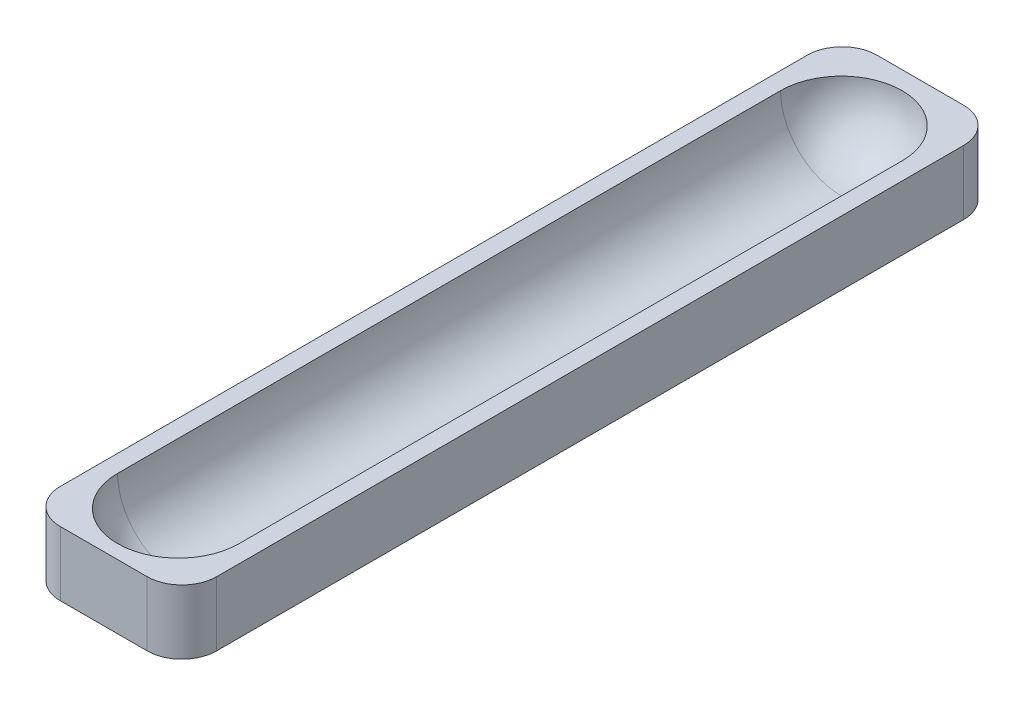
SolidWorks part; units mm, degrees
material "AISI 4340 Steel, normalized"
ref_plane "Front Plane" through (0, 0, 0) normal (0, 0, 1) x (1, 0, 0)
ref_plane "Top Plane" through (0, 0, 0) normal (0, 1, 0) x (1, 0, 0)
ref_plane "Right Plane" through (0, 0, 0) normal (1, 0, 0) x (0, 0, -1)
sketch "Sketch1" plane through (0, 0, 0) normal (0, 1, 0) x (1, 0, 0)
  line L0 (-57.15, 54.5595) -> (-57.15, 539.2088) construction
  line L1 (0, 0) -> (-114.3, 0)
  line L2 (0, 0) -> (0, 596.9)
  line L3 (0, 596.9) -> (-114.3, 596.9)
  line L4 (-114.3, 0) -> (-114.3, 596.9)
  line L5 (-101.6, 54.5595) -> (-101.6, 539.2088)
  line L6 (-12.7, 54.5595) -> (-12.7, 539.2088)
  arc A1 (-101.6, 54.5595) -> (-12.7, 54.5595) centre (-57.15, 54.5595) ccw
  arc A2 (-12.7, 539.2088) -> (-101.6, 539.2088) centre (-57.15, 539.2088) ccw
  point P7 (-101.6, 298.45)
  point P8 (-114.3, 298.45)
  point P10 (-57.15, 596.9)
  point P13 (-57.15, 342.9)
  point P15 (-57.15, 296.8841)
  dimension "D2" = 254
  dimension "D4" = 44.45
  dimension "D3" = 12.7
extrude "Boss-Extrude1" add sketch "Sketch1" along normal blind 46.99 contours L4 L1 L2 L3 | L6 A2 L5 A1 region at (-57.15, 0, -6.0775) region at (-57.15, 0, -296.8841)
sketch "Sketch2" plane through (0, 46.99, 0) normal (0, 1, 0) x (1, 0, 0)
  line L0 (-57.15, 596.9) -> (-57.15, 0) construction
  line L1 (0, 596.9) -> (-114.3, 596.9) construction
  line L2 (0, 0) -> (-114.3, 0) construction
  line L6 (-101.6, 539.2088) -> (-101.6, 54.5595)
  line L7 (-12.7, 54.5595) -> (-12.7, 539.2088)
  line L8 (-114.3, 0) -> (0, 0)
  line L9 (-114.3, 596.9) -> (-114.3, 0)
  line L10 (0, 596.9) -> (-114.3, 596.9)
  line L11 (0, 0) -> (0, 596.9)
  line L12 (-114.3, 0) -> (0, 0)
  line L13 (-114.3, 596.9) -> (-114.3, 0)
  line L14 (0, 596.9) -> (-114.3, 596.9)
  line L15 (0, 0) -> (0, 596.9)
  line L16 (-101.6, 539.2088) -> (-101.6, 54.5595)
  line L17 (-12.7, 54.5595) -> (-12.7, 539.2088)
  arc A3 (-12.7, 539.2088) -> (-101.6, 539.2088) centre (-57.15, 539.2088) ccw
  arc A4 (-101.6, 54.5595) -> (-12.7, 54.5595) centre (-57.15, 54.5595) ccw
  arc A5 (-12.7, 539.2088) -> (-101.6, 539.2088) centre (-57.15, 539.2088) ccw
  arc A6 (-101.6, 54.5595) -> (-12.7, 54.5595) centre (-57.15, 54.5595) ccw
  dimension "D2" = 0
  dimension "D3" = 0
revolve "Cut-Revolve1" cut sketch "Sketch2" angle 180 about L0 region at (-35.3481, 46.99, -296.8841) reverse direction yes
sketch "Sketch5" plane through (0, 0, 0) normal (0, -1, 0) x (1, 0, 0)
  line L0 (-57.15, 0) -> (-57.15, -596.9) construction
  line L1 (0, 0) -> (-114.3, 0) construction
  line L2 (0, -596.9) -> (-114.3, -596.9) construction
  line L3 (-57.15, -298.45) -> (0, -298.45) construction
  line L4 (0, 0) -> (0, -596.9) construction
  line L5 (-57.15, -298.45) -> (-114.3, -298.45) construction
  line L6 (-114.3, 0) -> (-114.3, -596.9) construction
  line L7 (-114.3, -44.45) -> (0, -44.45) construction
  line L8 (-114.3, -552.45) -> (0, -552.45) construction
  point P17 (-57.15, -44.45)
  point P18 (-57.15, -552.45)
  point P19 (-57.15, -298.45)
  dimension "D1" = 44.45
  dimension "D2" = 44.45
fillet "Fillet1" radius 25.4 4 edges at (0, 23.495, 0) (-114.3, 23.495, 0) (-114.3, 23.495, -596.9) (0, 23.495, -596.9)
sketch "Sketch3" [suppressed] plane through (0, 0, 0) normal (0, -1, 0) x (1, 0, 0)
  line L0 (-57.15, -114.3) -> (-57.15, 0) construction
  line L1 (-25.4, -114.3) -> (-88.9, -114.3) construction
  line L2 (-25.4, 0) -> (-88.9, 0) construction
  line L3 (0, -57.15) -> (-114.3, -57.15) construction
  line L4 (0, -25.4) -> (0, -88.9) construction
  line L5 (-114.3, -25.4) -> (-114.3, -88.9) construction
sketch "Sketch4" [suppressed] plane through (0, 0, 0) normal (0, -1, 0) x (1, 0, 0)
  line L0 (0, -57.15) -> (-114.3, -57.15) construction
  line L1 (0, -25.4) -> (0, -88.9) construction
  line L2 (-114.3, -25.4) -> (-114.3, -88.9) construction
  line L3 (-57.15, -114.3) -> (-57.15, 0) construction
  line L4 (-25.4, -114.3) -> (-88.9, -114.3) construction
  line L5 (-25.4, 0) -> (-88.9, 0) construction
  point P12 (-57.15, -57.15)
